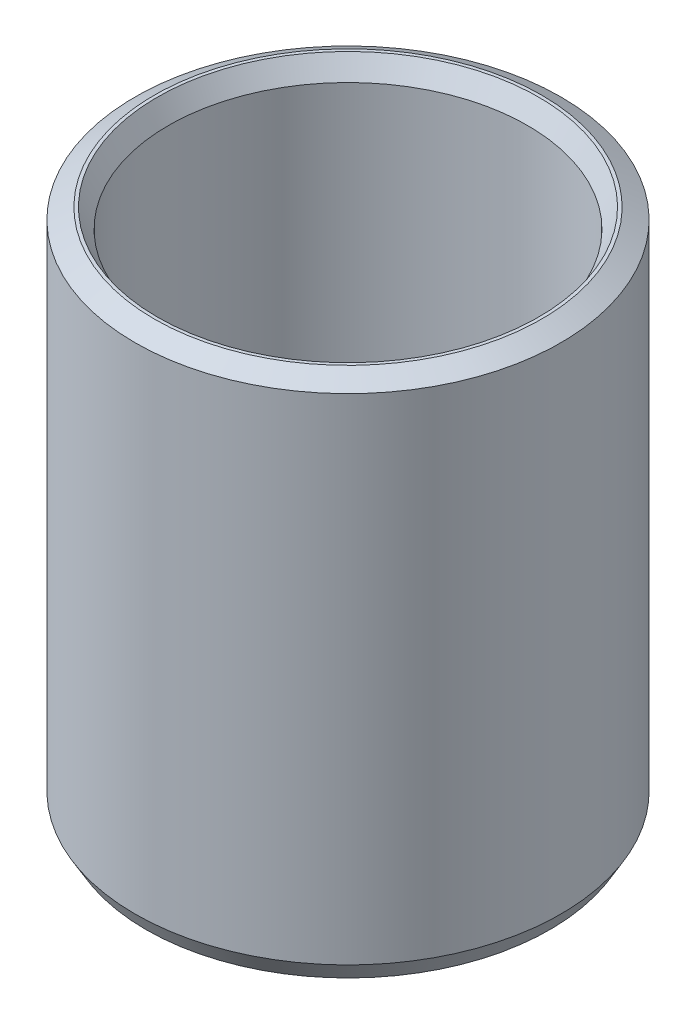
SolidWorks part; units mm, degrees
ref_plane "Front Plane" through (0, 0, 0) normal (0, 0, 1) x (1, 0, 0)
ref_plane "Top Plane" through (0, 0, 0) normal (0, 1, 0) x (1, 0, 0)
ref_plane "Right Plane" through (0, 0, 0) normal (1, 0, 0) x (0, 0, -1)
sketch "Sketch1" plane through (0, 0, 0) normal (0, 1, 0) x (1, 0, 0)
  circle A0 centre (0, 0) radius 37.5
  dimension "SLEEVE_OD" = 75
extrude "Boss-Extrude1" add sketch "Sketch1" along normal blind 92.4407
sketch "Sketch2" plane through (0, 0, 0) normal (0, 1, 0) x (1, 0, 0)
  circle A0 centre (0, 0) radius 31.6303
  dimension "BORE_D" = 63.2606
extrude "Cut-Extrude1" cut sketch "Sketch2" along normal through all
chamfer "Chamfer1" distance 1.9405 angle 60 4 edges at (0, 92.4407, 31.6303) (0, 0, 31.6303) (0, 0, 37.5) (0, 92.4407, 37.5) first distance on face at (0, 92.4407, 31.6303) first distance on face at (0, 0, 31.6303) first distance on face at (0, 92.4407, 37.5)
